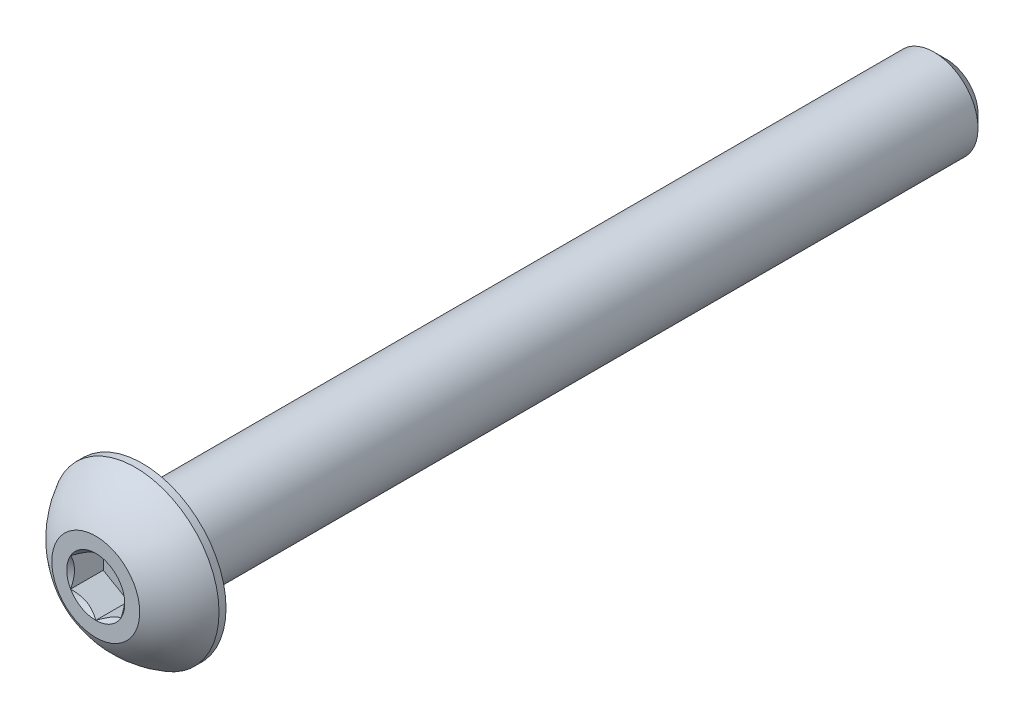
SolidWorks part; units mm, degrees
material "AISI 304"
ref_plane "Front" through (0, 0, 0) normal (0, 0, 1) x (1, 0, 0)
ref_plane "Top" through (0, 0, 0) normal (0, 1, 0) x (1, 0, 0)
ref_plane "Right" through (0, 0, 0) normal (1, 0, 0) x (0, 0, -1)
sketch "Sketch1" plane through (0, 0, 0) normal (1, 0, 0) x (0, 0, -1)
  line L2 (2.2098, 2.0828) -> (40.3098, 2.0828)
  line L3 (40.3098, 2.0828) -> (40.3098, 0)
  line L4 (40.3098, 0) -> (2.2098, 0)
  line L6 (1.8783, 3.9624) -> (2.2098, 3.9624) construction
  line L7 (40.3098, 2.0828) -> (40.3098, -2.0828) construction
  line L8 (0, 0) -> (2.2098, 0) construction
  line L9 (2.2098, 3.9624) -> (2.2098, -3.9624) construction
  line L11 (2.2098, 2.0828) -> (2.2098, 0)
  line L13 (0, 1.1906) -> (0, -1.1906) construction
  line L14 (0, 1.1906) -> (0, 2.0828) construction
  arc A3 (0, 2.0828) -> (1.8783, 3.9624) centre (3.9638, 0) cw construction
  dimension "D1" = 0.3315
revolve "Revolve1" add sketch "Sketch1" angle 360 mid plane about L4
sketch "Sketch3" plane through (0, 0, -40.3098) normal (0, 0, -1) x (-1, 0, 0)
  circle A0 centre (0, 0) radius 2.0828
curve "Helix/Spiral1" pitch 0.7937 height 45.3898 turns 57.184
sketch "Sketch2" plane through (0, 0, 0) normal (1, 0, 0) x (0, 0, -1)
  line L0 (40.3098, 2.0828) -> (41.0043, 2.0828)
  line L1 (41.0043, 2.0828) -> (40.7067, 1.5672)
  line L2 (40.7067, 1.5672) -> (40.6075, 1.5672)
  line L3 (40.6075, 1.5672) -> (40.3098, 2.0828)
  line L4 (40.4586, 1.825) -> (40.8555, 1.825) construction
  dimension "D1" = 60
  dimension "D2" = 0.0992
  dimension "D3" = 0.3969
chamfer "Chamfer1" distance 0.5953 angle 45 1 edges at (0, 2.0828, -40.3098)
sweep "Cut-Sweep1" [suppressed] cut profiles "Sketch2" path "Helix/Spiral1"
sketch "Sketch7" plane through (0, 0, 0) normal (1, 0, 0) x (0, 0, -1)
  line L6 (1.8783, 3.9624) -> (2.2098, 3.9624) construction
  line L8 (0, 0) -> (2.2098, 0) construction
  line L11 (2.2098, 3.9624) -> (2.2098, -3.9624) construction
  line L12 (1.8783, 3.9624) -> (2.2098, 3.9624)
  line L13 (0, 0) -> (2.2098, 0)
  line L14 (0, 1.1906) -> (0, -1.1906) construction
  line L15 (2.2098, 3.9624) -> (2.2098, 0)
  line L16 (0, 2.0828) -> (0, 0)
  arc A2 (1.8783, 3.9624) -> (0, 2.0828) centre (3.9638, 0) ccw construction
  arc A3 (1.8783, 3.9624) -> (0, 2.0828) centre (3.9638, 0) ccw
revolve "Revolve2" add sketch "Sketch7" angle 360 mid plane about L13
sketch "Sketch5" plane through (0, 0, 0) normal (0, 0, 1) x (1, 0, 0)
  line L1 (1.1906, -0.6874) -> (1.1906, 0.6874)
  line L2 (1.1906, 0.6874) -> (0, 1.3748)
  line L3 (0, 1.3748) -> (-1.1906, 0.6874)
  line L4 (-1.1906, 0.6874) -> (-1.1906, -0.6874)
  line L5 (-1.1906, -0.6874) -> (0, -1.3748)
  line L6 (0, -1.3748) -> (1.1906, -0.6874)
  circle A0 centre (0, 0) radius 1.1906 construction
extrude "Cut-Extrude2" cut sketch "Sketch5" against normal blind 1.5469
sketch "Sketch6" plane through (0, 0, 0) normal (0, 0, 1) x (1, 0, 0)
  circle A0 centre (0, 0) radius 1.3748
extrude "Cut-Extrude3" cut sketch "Sketch6" against normal blind 1.5469 draft 45
sketch "Sketch9" [suppressed] plane through (0, 0, -2.2098) normal (0, 0, 1) x (1, 0, 0)
  circle A2 centre (0, 0) radius 2.0828
extrude "Boss-Extrude2" [suppressed] add sketch "Sketch9" against normal offset from surface (19.05 mm away) 19.05
sketch "Sketch10" plane through (0, 0, 0) normal (1, 0, 0) x (0, 0, -1)
  line L0 (40.3098, 2.0828) -> (40.3098, -2.0828) construction
  point P0 (39.1192, -2.0828)
  dimension "D1" = 1.1906
equation "\"D3@Helix/Spiral1\" = \"Lg@Sketch1\" + \"Head Ht@Sketch1\" + .2"
equation "\"D2@Sketch2\" = \"D4@Helix/Spiral1\" * .125"
equation "\"D3@Sketch2\" = \"D4@Helix/Spiral1\" * .5"
equation "\"D1@Chamfer1\" = \"D4@Helix/Spiral1\" * .75"
equation "\"D1@Cut-Extrude2\" = \"Head Ht@Sketch1\" * .7"
equation "\"D1@Sketch1\" = \"Head Ht@Sketch1\" * .15"
equation "\"D1@Sketch10\" = \"D4@Helix/Spiral1\" * 1.5"
equation "\"D1@Cut-Extrude3\" = \"D1@Cut-Extrude2\""
